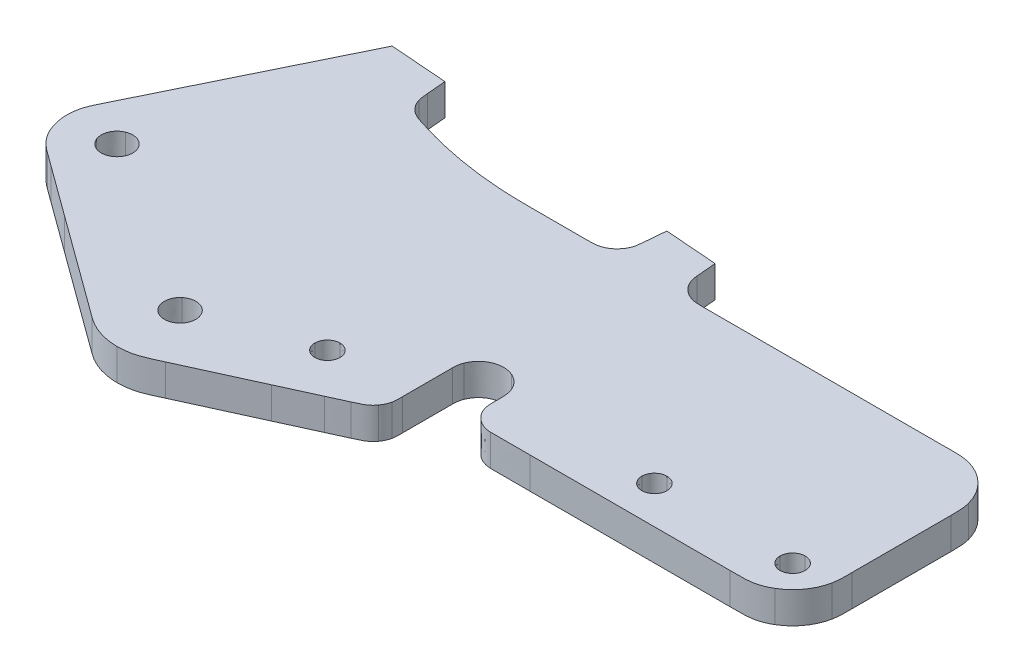
SolidWorks part; units mm, degrees
ref_plane "Front Plane" through (0, 0, 0) normal (0, 0, 1) x (1, 0, 0)
ref_plane "Top Plane" through (0, 0, 0) normal (0, 1, 0) x (1, 0, 0)
ref_plane "Right Plane" through (0, 0, 0) normal (1, 0, 0) x (0, 0, -1)
sketch "Sketch1" plane through (0, 0, 0) normal (0, 1, 0) x (1, 0, 0)
  line L0 (26.2542, 100.7033) -> (40.6892, 99.5939)
  line L1 (101.4193, 94.9221) -> (114.6416, 93.9093)
  line L2 (47.6413, 3.4801) -> (47.6414, 3.4827)
  spline S0 degree 3 poles (47.6414, 3.4827) (39.1389, 9.6839) (30.6295, 15.885) (22.127, 22.0862) knots 0 0 0 0 1 1 1 1
  spline S1 degree 3 poles (22.127, 22.0862) (17.8826, 25.1868) (13.6314, 28.2805) (9.387, 31.381) knots 0 0 0 0 1 1 1 1
  spline S2 degree 3 poles (9.387, 31.381) (8.3259, 32.1527) (7.2649, 32.9314) (6.2038, 33.703) knots 0 0 0 0 1 1 1 1
  spline S3 degree 3 poles (6.2038, 33.703) (5.1358, 34.4816) (4.1092, 35.274) (3.241, 36.2938) knots 0 0 0 0 1 1 1 1
  spline S4 degree 3 poles (3.241, 36.2938) (1.5184, 38.3195) (0.478, 40.8275) (0.2644, 43.4803) knots 0 0 0 0 1 1 1 1
  spline S5 degree 3 poles (0.2644, 43.4803) (0.1542, 44.8307) (0.2503, 46.1192) (0.5607, 47.4421) knots 0 0 0 0 1 1 1 1
  spline S6 degree 3 poles (0.5607, 47.4421) (0.8639, 48.7374) (1.4082, 49.9088) (1.987, 51.0939) knots 0 0 0 0 1 1 1 1
  spline S7 degree 3 poles (1.987, 51.0939) (3.1445, 53.4435) (4.2883, 55.793) (5.4458, 58.1494) knots 0 0 0 0 1 1 1 1
  spline S8 degree 3 poles (5.4458, 58.1494) (7.7541, 62.8762) (10.0691, 67.6097) (12.3774, 72.3363) knots 0 0 0 0 1 1 1 1
  spline S9 degree 3 poles (12.3774, 72.3363) (17.0007, 81.7897) (21.624, 91.2499) (26.2542, 100.7033) knots 0 0 0 0 1 1 1 1
  spline S10 degree 3 poles (40.6892, 99.5939) (40.8338, 97.9679) (40.9716, 96.3487) (41.1164, 94.7226) knots 0 0 0 0 1 1 1 1
  spline S11 degree 3 poles (41.1164, 94.7226) (41.1853, 93.9164) (41.2197, 93.1172) (41.454, 92.3317) knots 0 0 0 0 1 1 1 1
  spline S12 degree 3 poles (41.454, 92.3317) (41.6951, 91.498) (42.0741, 90.7883) (42.6184, 90.1131) knots 0 0 0 0 1 1 1 1
  spline S13 degree 3 poles (42.6184, 90.1131) (43.7691, 88.7006) (45.2091, 88.1907) (46.8214, 87.6808) knots 0 0 0 0 1 1 1 1
  spline S14 degree 3 poles (46.8214, 87.6808) (48.3717, 87.1779) (49.9358, 86.7231) (51.5205, 86.3028) knots 0 0 0 0 1 1 1 1
  spline S15 degree 3 poles (51.5205, 86.3028) (57.9078, 84.6009) (64.3087, 83.5467) (70.9027, 83.1058) knots 0 0 0 0 1 1 1 1
  spline S16 degree 3 poles (70.9027, 83.1058) (74.1824, 82.8853) (77.4552, 82.8782) (80.7349, 82.8782) knots 0 0 0 0 1 1 1 1
  spline S17 degree 3 poles (80.7349, 82.8782) (84.0147, 82.8782) (87.2944, 82.8782) (90.5742, 82.8782) knots 0 0 0 0 1 1 1 1
  spline S18 degree 3 poles (90.5742, 82.8782) (91.146, 82.8782) (94.7841, 82.8583) (95.3559, 82.9332) knots 0 0 0 0 1 1 1 1
  spline S19 degree 3 poles (95.3559, 82.9332) (97.0441, 83.1467) (98.5737, 84.0357) (99.6072, 85.393) knots 0 0 0 0 1 1 1 1
  spline S20 degree 3 poles (99.6072, 85.393) (100.813, 86.9778) (100.8336, 88.1973) (100.9921, 90.037) knots 0 0 0 0 1 1 1 1
  spline S21 degree 3 poles (100.9921, 90.037) (101.1368, 91.67) (101.2815, 93.2961) (101.4193, 94.9221) knots 0 0 0 0 1 1 1 1
  spline S22 degree 3 poles (114.6416, 93.9093) (114.7863, 92.235) (114.931, 90.5675) (115.0757, 88.8932) knots 0 0 0 0 1 1 1 1
  spline S23 degree 3 poles (115.0757, 88.8932) (115.248, 86.9985) (115.8336, 85.6411) (117.3081, 84.3939) knots 0 0 0 0 1 1 1 1
  spline S24 degree 3 poles (117.3081, 84.3939) (118.7688, 83.1537) (120.2571, 82.8781) (122.0761, 82.8781) knots 0 0 0 0 1 1 1 1
  spline S25 degree 3 poles (122.0761, 82.8781) (123.7573, 82.8781) (125.4316, 82.8781) (127.1128, 82.8781) knots 0 0 0 0 1 1 1 1
  spline S26 degree 3 poles (127.1128, 82.8781) (133.8307, 82.8781) (140.5487, 82.8781) (147.2666, 82.8781) knots 0 0 0 0 1 1 1 1
  spline S27 degree 3 poles (147.2666, 82.8781) (154.019, 82.8781) (160.7783, 82.8781) (167.5307, 82.8781) knots 0 0 0 0 1 1 1 1
  spline S28 degree 3 poles (167.5307, 82.8781) (170.9069, 82.8781) (174.2831, 82.8781) (177.6662, 82.8781) knots 0 0 0 0 1 1 1 1
  spline S29 degree 3 poles (177.6662, 82.8781) (179.3543, 82.8781) (181.0424, 82.8781) (182.7304, 82.8781) knots 0 0 0 0 1 1 1 1
  spline S30 degree 3 poles (182.7304, 82.8781) (184.3979, 82.8781) (186.0653, 82.9677) (187.7327, 82.8431) knots 0 0 0 0 1 1 1 1
  spline S31 degree 3 poles (187.7327, 82.8431) (191.2467, 82.5882) (194.492, 80.8932) (196.7106, 78.1509) knots 0 0 0 0 1 1 1 1
  spline S32 degree 3 poles (196.7106, 78.1509) (197.8475, 76.7385) (198.6054, 75.2571) (199.0809, 73.5069) knots 0 0 0 0 1 1 1 1
  spline S33 degree 3 poles (199.0809, 73.5069) (199.5218, 71.8877) (199.5218, 70.2892) (199.5218, 68.6493) knots 0 0 0 0 1 1 1 1
  spline S34 degree 3 poles (199.5218, 68.6493) (199.5218, 61.9934) (199.5218, 55.3237) (199.5218, 48.6609) knots 0 0 0 0 1 1 1 1
  spline S35 degree 3 poles (199.5218, 48.6609) (199.5218, 46.9935) (199.5218, 45.326) (199.5218, 43.6655) knots 0 0 0 0 1 1 1 1
  spline S36 degree 3 poles (199.5218, 43.6655) (199.5218, 42.0325) (199.5977, 40.4202) (199.2669, 38.7941) knots 0 0 0 0 1 1 1 1
  spline S37 degree 3 poles (199.2669, 38.7941) (198.5434, 35.2871) (196.3799, 32.2484) (193.3, 30.4225) knots 0 0 0 0 1 1 1 1
  spline S38 degree 3 poles (193.3, 30.4225) (189.8273, 28.3693) (187.3193, 28.6449) (183.5986, 28.6449) knots 0 0 0 0 1 1 1 1
  spline S39 degree 3 poles (183.5986, 28.6449) (180.2706, 28.6449) (176.9357, 28.6449) (173.6078, 28.6449) knots 0 0 0 0 1 1 1 1
  spline S40 degree 3 poles (173.6078, 28.6449) (160.0961, 28.6449) (146.5845, 28.6449) (133.0728, 28.6449) knots 0 0 0 0 1 1 1 1
  spline S41 degree 3 poles (133.0728, 28.6449) (129.7724, 28.6449) (126.472, 28.5689) (123.1647, 28.6499) knots 0 0 0 0 1 1 1 1
  spline S42 degree 3 poles (123.1647, 28.6499) (121.4353, 28.6899) (119.8023, 29.4354) (118.631, 30.7169) knots 0 0 0 0 1 1 1 1
  spline S43 degree 3 poles (118.631, 30.7169) (117.3632, 32.1156) (116.9773, 33.535) (116.9773, 35.3609) knots 0 0 0 0 1 1 1 1
  spline S44 degree 3 poles (116.9773, 35.3609) (116.9773, 36.739) (117.1013, 38.8543) (116.6121, 40.2392) knots 0 0 0 0 1 1 1 1
  spline S45 degree 3 poles (116.6121, 40.2392) (116.0196, 41.9273) (114.7449, 43.2846) (113.0981, 43.9805) knots 0 0 0 0 1 1 1 1
  spline S46 degree 3 poles (113.0981, 43.9805) (109.7839, 45.3792) (105.9943, 43.767) (104.699, 40.4115) knots 0 0 0 0 1 1 1 1
  spline S47 degree 3 poles (104.699, 40.4115) (104.3889, 39.6122) (104.2718, 38.8198) (104.2718, 37.9723) knots 0 0 0 0 1 1 1 1
  spline S48 degree 3 poles (104.2718, 37.9723) (104.2718, 37.1248) (104.2718, 36.2842) (104.2718, 35.4436) knots 0 0 0 0 1 1 1 1
  spline S49 degree 3 poles (104.2718, 35.4436) (104.2718, 33.7555) (104.2718, 32.0674) (104.2718, 30.3793) knots 0 0 0 0 1 1 1 1
  spline S50 degree 3 poles (104.2718, 30.3793) (104.2718, 28.6912) (104.2718, 27.0031) (104.2718, 25.315) knots 0 0 0 0 1 1 1 1
  spline S51 degree 3 poles (104.2718, 25.315) (104.2718, 24.4813) (104.3133, 23.6545) (104.134, 22.8139) knots 0 0 0 0 1 1 1 1
  spline S52 degree 3 poles (104.134, 22.8139) (103.9411, 21.9319) (103.6035, 21.174) (103.0798, 20.4436) knots 0 0 0 0 1 1 1 1
  spline S53 degree 3 poles (103.0798, 20.4436) (101.9843, 18.9209) (100.4891, 18.3422) (98.9181, 17.6256) knots 0 0 0 0 1 1 1 1
  spline S54 degree 3 poles (98.9181, 17.6256) (97.3885, 16.9297) (95.852, 16.2269) (94.3155, 15.531) knots 0 0 0 0 1 1 1 1
  spline S55 degree 3 poles (94.3155, 15.531) (91.2425, 14.1253) (88.1694, 12.7266) (85.1033, 11.3279) knots 0 0 0 0 1 1 1 1
  spline S56 degree 3 poles (85.1033, 11.3279) (78.9917, 8.5443) (72.8801, 5.7607) (66.7754, 2.977) knots 0 0 0 0 1 1 1 1
  spline S57 degree 3 poles (66.7754, 2.977) (63.3027, 1.3992) (61.1875, 0.1934) (57.1567, 0.221) knots 0 0 0 0 1 1 1 1
  spline S58 degree 3 poles (57.1567, 0.221) (53.7185, 0.251) (50.3767, 1.3923) (47.6413, 3.4801) knots 0 0 0 0 1 1 1 1
  spline S59 degree 3 poles (193.176, 38.1335) (193.176, 39.8835) (191.7566, 41.3098) (189.9996, 41.3098) knots 0 0 0 0 1 1 1 1
  spline S60 degree 3 poles (189.9996, 41.3098) (188.2495, 41.3098) (186.8232, 39.8835) (186.8232, 38.1335) knots 0 0 0 0 1 1 1 1
  spline S61 degree 3 poles (186.8232, 38.1335) (186.8232, 36.3764) (188.2495, 34.9571) (189.9996, 34.9571) knots 0 0 0 0 1 1 1 1
  spline S62 degree 3 poles (189.9996, 34.9571) (191.7566, 34.9571) (193.176, 36.3764) (193.176, 38.1335) knots 0 0 0 0 1 1 1 1
  spline S63 degree 3 poles (60.3193, 18.648) (58.9137, 20.3292) (56.4057, 20.5497) (54.7314, 19.137) knots 0 0 0 0 1 1 1 1
  spline S64 degree 3 poles (54.7314, 19.137) (53.0502, 17.7314) (52.8297, 15.2234) (54.2353, 13.549) knots 0 0 0 0 1 1 1 1
  spline S65 degree 3 poles (54.2353, 13.549) (55.6478, 11.8678) (58.1558, 11.6542) (59.8301, 13.06) knots 0 0 0 0 1 1 1 1
  spline S66 degree 3 poles (59.8301, 13.06) (61.5113, 14.4656) (61.7249, 16.9737) (60.3193, 18.648) knots 0 0 0 0 1 1 1 1
  spline S67 degree 3 poles (87.8043, 25.9654) (87.8043, 27.7155) (86.3849, 29.1349) (84.6348, 29.1349) knots 0 0 0 0 1 1 1 1
  spline S68 degree 3 poles (84.6348, 29.1349) (82.8778, 29.1349) (81.4584, 27.7155) (81.4584, 25.9654) knots 0 0 0 0 1 1 1 1
  spline S69 degree 3 poles (81.4584, 25.9654) (81.4584, 24.2084) (82.8778, 22.789) (84.6348, 22.789) knots 0 0 0 0 1 1 1 1
  spline S70 degree 3 poles (84.6348, 22.789) (86.3849, 22.789) (87.8043, 24.2084) (87.8043, 25.9654) knots 0 0 0 0 1 1 1 1
  spline S71 degree 3 poles (158.2496, 38.1335) (158.2496, 39.8835) (156.8302, 41.3098) (155.0732, 41.3098) knots 0 0 0 0 1 1 1 1
  spline S72 degree 3 poles (155.0732, 41.3098) (153.3231, 41.3098) (151.8969, 39.8835) (151.8969, 38.1335) knots 0 0 0 0 1 1 1 1
  spline S73 degree 3 poles (151.8969, 38.1335) (151.8969, 36.3764) (153.3231, 34.9571) (155.0732, 34.9571) knots 0 0 0 0 1 1 1 1
  spline S74 degree 3 poles (155.0732, 34.9571) (156.8302, 34.9571) (158.2496, 36.3764) (158.2496, 38.1335) knots 0 0 0 0 1 1 1 1
  spline S75 degree 3 poles (16.5804, 46.0434) (15.7398, 48.0622) (13.4178, 49.0269) (11.399, 48.1862) knots 0 0 0 0 1 1 1 1
  spline S76 degree 3 poles (11.399, 48.1862) (9.3732, 47.3525) (8.4086, 45.0305) (9.2492, 43.0048) knots 0 0 0 0 1 1 1 1
  spline S77 degree 3 poles (9.2492, 43.0048) (10.0898, 40.9791) (12.4118, 40.0144) (14.4307, 40.8551) knots 0 0 0 0 1 1 1 1
  spline S78 degree 3 poles (14.4307, 40.8551) (16.4564, 41.6957) (17.421, 44.0177) (16.5804, 46.0434) knots 0 0 0 0 1 1 1 1
extrude "Boss-Extrude1" add sketch "Sketch1" along normal blind 7.9375
sketch "Sketch2" plane through (7.8204, 0, -102.092) normal (0.0764, 0, -0.9971) x (-0.9971, 0, -0.0764)
  line L0 (-100.5036, 3.9688) -> (-26.3356, 3.9688) construction
  line L1 (-93.8731, 7.9375) -> (-107.1341, 7.9375) construction
  line L2 (-93.8731, 7.9375) -> (-93.8731, 0) construction
  line L3 (-93.8731, 0) -> (-107.1341, 0) construction
  line L4 (-107.1341, 7.9375) -> (-107.1341, 0) construction
  line L5 (-93.8731, 7.9375) -> (-107.1341, 0) construction
  line L6 (-93.8731, 0) -> (-107.1341, 7.9375) construction
  point P4 (-100.5036, 3.9688)
  dimension "D1" = 74.168
sketch "Sketch5" plane through (7.8481, 0, -102.1179) normal (0.0766, 0, -0.9971) x (-0.9971, 0, -0.0766)
  point P0 (-26.31, 3.9688)
hole_wizard "M6x1.0 Tapped Hole5" positions "3DSketch2" profile "Sketch4" tap size "M6x1.0" standard "ANSI Metric"
sketch3d "3DSketch2"
  point P0 (108.0305, 3.9688, -94.4157)
  point P3 (34.0808, 3.9688, -100.1018)
sketch "Sketch4" plane through (108.0305, 3.9688, -94.4157) normal (0, 1, 0) x (-0.9971, 0, -0.0764)
  line L0 (0, 0) -> (0, 13.5022)
  line L1 (0, 13.5022) -> (2.5, 12)
  line L2 (2.5, 12) -> (2.5, 0.525)
  line L3 (2.5, 0.525) -> (3.025, 0)
  line L5 (3.025, 0) -> (0, 0)
  line L6 (-2.5, 0.525) -> (-3.025, 0) construction
  line L10 (0, 13.5022) -> (-2.5, 12) construction
  line L11 (0, -6.35) -> (0, 107.95) construction
  dimension "Tap Drill Dia." = 5
  dimension "Tap Drill Depth" = 12
  dimension "Near C'Sink Dia." = 6.05
  dimension "Near C'Sink Angle" = 90
  dimension "Drill Angle" = 118
cosmetic thread "Hole Thread2" parameters "D1"=11.938, "D2"=6
cosmetic thread "Hole Thread3" parameters "D1"=11.938, "D2"=6
sketch "Sketch6" plane through (0, 7.9375, 0) normal (0, 1, 0) x (1, 0, 0)
  circle A0 centre (12.9155, 44.5224) radius 3.968
  circle A1 centre (57.2711, 16.0995) radius 3.9733
  circle A2 centre (84.6314, 25.962) radius 3.1729
  circle A3 centre (155.0732, 38.1335) radius 3.1764
  circle A4 centre (189.9996, 38.1335) radius 3.1764
  spline S0 degree 3 poles (60.3193, 18.648) (58.9137, 20.3292) (56.4057, 20.5497) (54.7314, 19.137) knots 0 0 0 0 1 1 1 1 construction
